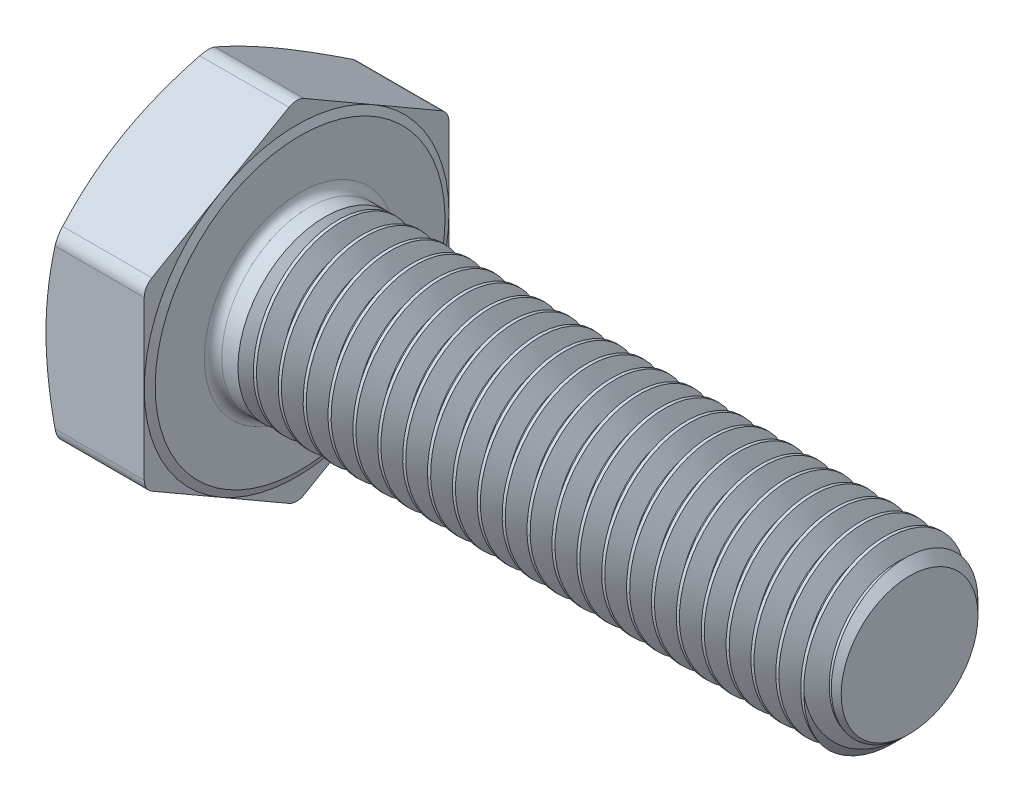
SolidWorks part; units mm, degrees
ref_plane "Front Plane" through (0, 0, 0) normal (0, 0, 1) x (1, 0, 0)
ref_plane "Top Plane" through (0, 0, 0) normal (0, 1, 0) x (1, 0, 0)
ref_plane "Right Plane" through (0, 0, 0) normal (1, 0, 0) x (0, 0, -1)
sketch "Sketch1" plane through (0, 0, 0) normal (0, 0, 1) x (1, 0, 0)
  line L0 (0, 0) -> (22.225, 0) construction
  line L1 (0, 0) -> (-3.9688, 0) construction
  line L2 (0, 5.5562) -> (0, -5.5562) construction
  line L3 (-3.9688, 5.5562) -> (-3.9687, -5.5563) construction
  line L4 (22.225, 3.175) -> (22.225, -3.175) construction
  line L8 (21.3179, 3.175) -> (22.225, 3.175) construction
  point P8 (21.3179, 0)
  point P11 (19.05, -3.175)
  point P12 (0.9071, 0)
  dimension "Head Height" = 3.9688
  dimension "Head Width" = 11.1125
  dimension "Length" = 22.225
  dimension "Thread Size" = 6.35
  dimension "D1" = 3.175
  dimension "Thread Pitch" = 0.9071
  dimension "D2" = 0.9071
sketch "Sketch2" plane through (0, 0, 0) normal (1, 0, 0) x (0, 0, -1)
  circle A0 centre (0, 0) radius 3.175
extrude "Boss-Extrude1" add sketch "Sketch2" along normal up to vertex (22.225 mm away) up to point (22.225, 3.175, 0)
sketch "Sketch3" plane through (0, 0, 0) normal (-1, 0, 0) x (0, 0, 1)
  line L0 (0, 6.4158) -> (0, 0) construction
  line L1 (0, 6.4158) -> (-5.5563, 3.2079)
  line L2 (-5.5563, 3.2079) -> (-5.5563, -3.2079)
  line L3 (-5.5563, -3.2079) -> (0, -6.4158)
  line L4 (0, -6.4158) -> (5.5562, -3.2079)
  line L5 (5.5562, -3.2079) -> (5.5562, 3.2079)
  line L6 (5.5562, 3.2079) -> (0, 6.4158)
  circle A0 centre (0, 0) radius 5.5562 construction
extrude "Boss-Extrude2" add sketch "Sketch3" along normal up to vertex (3.9688 mm away) up to point (-3.9688, 5.5562, 0)
sketch "Sketch5" plane through (-3.9688, 0, 0) normal (-1, 0, 0) x (0, 0, 1)
  circle A0 centre (0, 0) radius 5.5562 construction
  circle A1 centre (0, 0) radius 5.5562 construction
  circle A2 centre (0, 0) radius 5.0006
  dimension "D1" = 0.5556
extrude "Cut-Extrude1" cut sketch "Sketch5" against normal up to vertex (3.9688 mm away) draft 65 flip side to cut up to point (0, 0, 0)
sketch "Sketch11" plane through (-3.9688, 0, 0) normal (-1, 0, 0) x (0, 0, 1)
  line L0 (0, 3.9449) -> (0, 2.4448) construction
  line L1 (0.2223, 3.9449) -> (0.2223, 2.4448)
  line L2 (-0.2222, 3.9449) -> (-0.2222, 2.4448)
  arc A0 (0.2223, 3.9449) -> (-0.2222, 3.9449) centre (0, 3.9449) ccw
  arc A1 (-0.2222, 2.4448) -> (0.2223, 2.4448) centre (0, 2.4448) ccw
  circle A2 centre (0, 0) radius 4.1672 construction
  circle A3 centre (0, 0) radius 2.2225 construction
  point P3 (0, 3.1948)
  dimension "D1" = 8.3344
  dimension "D2" = 4.445
  dimension "D3" = 0.4445
extrude "Boss-Extrude5" add sketch "Sketch11" along normal blind 0.0635
fillet "Fillet5" radius 0.0635 4 edges at (-4.0323, 3.1948, 0.2223) (-4.0323, 2.2225, 0) (-4.0323, 3.1948, -0.2222) (-4.0323, 4.1672, 0)
pattern_circular "CirPattern1" count 6 over 360 about axis through (0, 0, 0) along (-1, 0, 0) of "Boss-Extrude5", "Fillet5" reverse direction yes
fillet "Fillet7" radius 0.5556 6 edges at (-1.6544, -6.4158, 0) (-1.6544, -3.2079, -5.5563) (-1.6544, 3.2079, -5.5563) (-1.6544, 6.4158, 0) (-1.6544, -3.2079, 5.5562) (-1.6544, 3.2079, 5.5562)
chamfer "Chamfer1" distance 0.6804 angle 45 1 edges at (22.225, 0, -3.175)
sketch "Sketch15" plane through (0, 0, 0) normal (0, 0, 1) x (1, 0, 0)
  line L0 (0, 5.2839) -> (-0.127, 5.5562)
  line L1 (0, 5.5562) -> (0, -5.5562) construction
  line L2 (-0.127, 5.5562) -> (-0.127, 6.4158)
  line L3 (-0.127, 6.4158) -> (0, 6.4158)
  line L4 (0, 6.4158) -> (0, 5.2839)
  dimension "D1" = 0.127
  dimension "D2" = 25
revolve "Cut-Revolve1" cut sketch "Sketch15" angle 360 about L1
fillet "Fillet4" radius 0.3175 1 edges at (0, 0, 3.175)
sketch "Reference Sketch1" plane through (0, 0, 0) normal (1, 0, 0) x (0, 0, -1)
  line L1 (0, 6.4158) -> (-5.5563, 3.2079)
  line L2 (-5.5563, 3.2079) -> (-5.5563, -3.2079)
  line L3 (-5.5563, -3.2079) -> (0, -6.4158)
  line L4 (0, -6.4158) -> (5.5563, -3.2079)
  line L5 (5.5563, -3.2079) -> (5.5563, 3.2079)
  line L6 (5.5563, 3.2079) -> (0, 6.4158)
  circle A0 centre (0, 0) radius 5.5563 construction
  circle A1 centre (0, 0) radius 5.5562
sketch "Sketch12" plane through (22.225, 0, 0) normal (1, 0, 0) x (0, 0, -1)
  circle A1 centre (0, 0) radius 3.175
ref_plane "Plane2" through (0.9071, 0, 0) normal (1, 0, 0) x (0, 0, -1)
split "Split1" trim tools "Plane2" bodies to split 126 116 resulting bodies 118 119
curve "Helix/Spiral2" pitch 0.9071 height 23.1321 radius 3.175 centre (22.225, 0, 0) axis (-1, 0, 0) start towards (0, 1, 0) parameters "Pitch"=0.9071
sketch "Sketch13" plane through (0, 0, 0) normal (0, 0, 1) x (1, 0, 0)
  line L0 (22.1683, 3.2732) -> (22.6219, 2.4876) construction
  line L1 (22.6219, 2.4876) -> (23.0754, 3.2732) construction
  line L2 (23.0754, 3.2732) -> (22.1683, 3.2732) construction
  line L3 (22.6219, 2.4876) -> (22.6219, 2.5858) construction
  line L4 (22.225, 3.175) -> (23.0188, 3.175)
  line L5 (22.6219, 3.175) -> (22.6219, 3.2732) construction
  line L6 (23.0188, 3.175) -> (22.6786, 2.5858)
  line L7 (22.6786, 2.5858) -> (22.5652, 2.5858)
  line L8 (22.5652, 2.5858) -> (22.225, 3.175)
  line L9 (21.3179, 3.175) -> (22.225, 3.175) construction
  dimension "D1" = 0.1134
sweep "Cut-Sweep1" cut profiles "Sketch13" path "Helix/Spiral2" align with end faces yes
sketch "Sketch14" plane through (0.9071, 0, 0) normal (1, 0, 0) x (0, 0, -1)
  circle A1 centre (0, 0) radius 3.175
  circle A2 centre (0, 0) radius 3.175
  dimension "D1" = 0
extrude "Boss-Extrude4" add sketch "Sketch14" along normal through all draft 50
equation "\"D1@Sketch11\"=\"Head Width@Sketch1\" * 0.75"
equation "\"D2@Sketch11\"=\"Head Width@Sketch1\"*0.4"
equation "\"D3@Sketch11\"=\"Head Width@Sketch1\" * .04"
equation "\"D3@Helix/Spiral2\"=\"Length@Sketch1\" + \"Thread Pitch@Sketch1\""
equation "\"D1@Chamfer1\"=\"Thread Pitch@Sketch1\"*0.750"
equation "\"D1@Sketch1\"=\"Thread Pitch@Sketch1\"*3.5"
equation "\"Pitch@Helix/Spiral2\"=\"Thread Pitch@Sketch1\""
equation "\"D1@Sketch13\"=\"Thread Pitch@Sketch1\"*0.125"
equation "\"D1@Sketch5\"=\"Head Width@Sketch1\"*0.05"
equation "\"D1@Fillet4\"=\"Thread Size@Sketch1\"*0.05"
equation "\"D2@Sketch1\"=\"Thread Pitch@Sketch1\""
equation "\"D1@Fillet7\"=\"Head Width@Sketch1\"*0.05"
